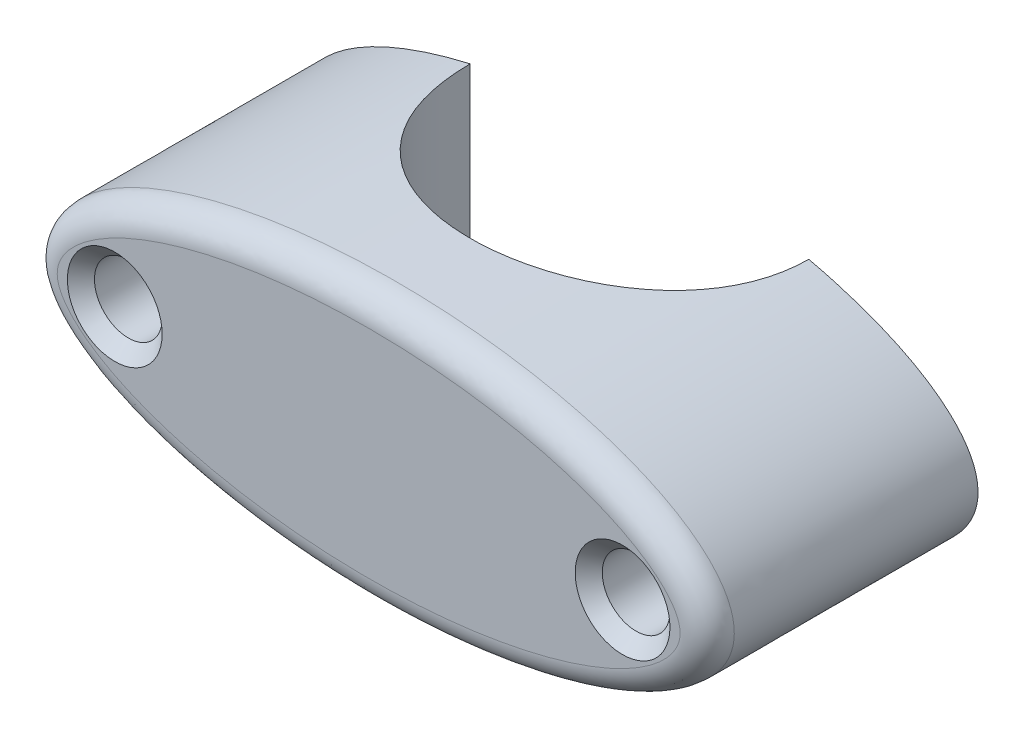
SolidWorks part; units mm, degrees
material "6061-T6 (SS)"
ref_plane "Front Plane" through (0, 0, 0) normal (1, 0, 0) x (0, 1, 0)
ref_plane "Top Plane" through (0, 0, 0) normal (0, 0, 1) x (0, 1, 0)
ref_plane "Right Plane" through (0, 0, 0) normal (0, 1, 0) x (-1, 0, 0)
sketch "Sketch2" plane through (0, 0, 0) normal (0, 0, 1) x (0, 1, 0)
  line L0 (0, 28.6198) -> (0, -33.4946) construction
  line L1 (-48.0081, 0) -> (58.9231, 0) construction
  ellipse E0 centre (0, 0) end of major axis (0, -25) minor radius 10
  point P15 (0, 29.1548)
  point P18 (0, -25)
  dimension "D1" = 20
  dimension "D2" = 50
extrude "Boss-Extrude1" add sketch "Sketch2" against normal blind 20 contours E0 region at (0, 0, 0)
sketch "Sketch3" plane through (0, 0, 0) normal (0, 1, 0) x (-1, 0, 0)
  line L0 (0, 2.896) -> (0, -25.1144) construction
  line L2 (-25, -20) -> (25, -20) construction
  circle A1 centre (0, -20) radius 12.5
  dimension "D1" = 25
extrude "Cut-Extrude1" cut sketch "Sketch3" against normal through all both and the other way through all
fillet "Fillet2" radius 2 1 edges at (25, 0, 0)
sketch "Sketch5" plane through (0, 0, 0) normal (0, 0, -1) x (1, 0, 0)
  line L0 (0, 5.4353) -> (0, -6.2879) construction
  line L2 (-12.5, -8.6603) -> (-12.5, 8.6603) construction
  circle A0 centre (-18.75, 0) radius 2.5
  circle A1 centre (18.75, 0) radius 2.5
  dimension "D1" = 5
  dimension "D2" = 6.25
extrude "Cut-Extrude3" cut sketch "Sketch5" against normal through all both and the other way through all
chamfer "Chamfer1" distance 1 angle 45 2 edges at (21.25, 0, 0) (-16.25, 0, 0)
equation "\"a\"= 5mm"
